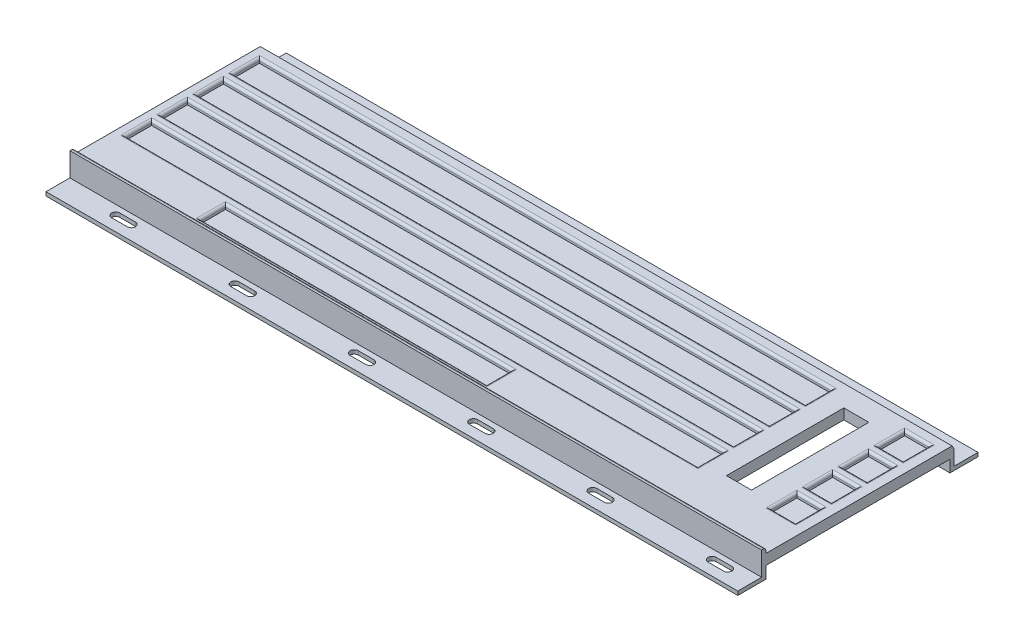
SolidWorks part; units mm, degrees
ref_plane "Front Plane" through (0, 0, 0) normal (0, 0, 1) x (1, 0, 0)
ref_plane "Top Plane" through (0, 0, 0) normal (0, 1, 0) x (1, 0, 0)
ref_plane "Right Plane" through (0, 0, 0) normal (1, 0, 0) x (0, 0, -1)
sketch "Sketch1" plane through (0, 0, 0) normal (0, 1, 0) x (1, 0, 0)
  line L1 (-184.15, 49.022) -> (184.15, 49.022)
  line L2 (-184.15, 49.022) -> (-184.15, -49.022)
  line L3 (-184.15, -49.022) -> (184.15, -49.022)
  line L4 (184.15, 49.022) -> (184.15, -49.022)
  line L5 (-184.15, 49.022) -> (184.15, -49.022) construction
  line L6 (-184.15, -49.022) -> (184.15, 49.022) construction
  point P0 (0, 0)
  dimension "D1" = 368.3
  dimension "D2" = 98.044
extrude "Boss-Extrude1" add sketch "Sketch1" along normal blind 3.175
sketch "Sketch2" plane through (0, 3.175, 0) normal (0, 1, 0) x (1, 0, 0)
  line L0 (184.15, -49.022) -> (184.15, 49.022) construction
  line L1 (-184.15, 49.022) -> (184.15, 49.022)
  line L2 (-184.15, 49.022) -> (-184.15, 44.577)
  line L3 (-184.15, 44.577) -> (184.15, 44.577)
  line L4 (184.15, 49.022) -> (184.15, 44.577)
  line L5 (-184.15, 49.022) -> (184.15, 44.577) construction
  line L6 (-184.15, 44.577) -> (184.15, 49.022) construction
  point P4 (0, 46.7995)
  dimension "D1" = 4.445
extrude "Boss-Extrude2" add sketch "Sketch2" along normal blind 2.3813
sketch "Sketch3" plane through (0, 3.175, 0) normal (0, 1, 0) x (1, 0, 0)
  line L0 (-184.15, 44.577) -> (-184.15, -49.022) construction
  line L1 (184.15, -49.022) -> (-184.15, -49.022)
  line L2 (184.15, -49.022) -> (184.15, -45.212)
  line L3 (184.15, -45.212) -> (-184.15, -45.212)
  line L4 (-184.15, -49.022) -> (-184.15, -45.212)
  line L5 (184.15, -49.022) -> (-184.15, -45.212) construction
  line L6 (184.15, -45.212) -> (-184.15, -49.022) construction
  point P5 (0, -47.117)
  dimension "D1" = 3.81
extrude "Boss-Extrude3" add sketch "Sketch3" along normal blind 2.3813
sketch "Sketch4" plane through (0, 3.175, 0) normal (0, 1, 0) x (1, 0, 0)
  line L0 (184.15, -45.212) -> (184.15, 44.577) construction
  line L1 (184.15, -31.877) -> (-184.15, -31.877)
  line L2 (184.15, -31.877) -> (184.15, -26.797)
  line L3 (184.15, -26.797) -> (-184.15, -26.797)
  line L4 (-184.15, -31.877) -> (-184.15, -26.797)
  line L5 (184.15, -31.877) -> (-184.15, -26.797) construction
  line L6 (184.15, -26.797) -> (-184.15, -31.877) construction
  line L7 (-184.15, 44.577) -> (-184.15, -45.212) construction
  point P4 (0, -29.337)
  dimension "D1" = 17.145
  dimension "D2" = 5.08
extrude "Boss-Extrude4" add sketch "Sketch4" along normal blind 2.3813
sketch "Sketch5" plane through (0, 3.175, 0) normal (0, 1, 0) x (1, 0, 0)
  line L0 (184.15, -26.797) -> (184.15, 44.577) construction
  line L1 (184.15, -12.827) -> (-184.15, -12.827)
  line L2 (184.15, -12.827) -> (184.15, -7.747)
  line L3 (184.15, -7.747) -> (-184.15, -7.747)
  line L4 (-184.15, -12.827) -> (-184.15, -7.747)
  line L5 (184.15, -12.827) -> (-184.15, -7.747) construction
  line L6 (184.15, -7.747) -> (-184.15, -12.827) construction
  line L7 (-184.15, 44.577) -> (-184.15, -26.797) construction
  point P4 (0, -10.287)
  dimension "D1" = 36.195
  dimension "D2" = 5.08
extrude "Boss-Extrude5" add sketch "Sketch5" along normal blind 2.3813
sketch "Sketch7" plane through (0, 3.175, 0) normal (0, 1, 0) x (1, 0, 0)
  line L0 (184.15, -7.747) -> (184.15, 44.577) construction
  line L1 (184.15, 6.223) -> (-184.15, 6.223)
  line L2 (184.15, 6.223) -> (184.15, 11.303)
  line L3 (184.15, 11.303) -> (-184.15, 11.303)
  line L4 (-184.15, 6.223) -> (-184.15, 11.303)
  line L5 (184.15, 6.223) -> (-184.15, 11.303) construction
  line L6 (184.15, 11.303) -> (-184.15, 6.223) construction
  line L7 (-184.15, 44.577) -> (-184.15, -7.747) construction
  point P4 (0, 8.763)
  dimension "D1" = 55.245
  dimension "D2" = 5.08
extrude "Boss-Extrude6" add sketch "Sketch7" along normal blind 2.3813
sketch "Sketch9" plane through (0, 3.175, 0) normal (0, 1, 0) x (1, 0, 0)
  line L0 (184.15, 11.303) -> (184.15, 44.577) construction
  line L1 (184.15, 25.4) -> (-184.15, 25.4)
  line L2 (184.15, 25.4) -> (184.15, 30.48)
  line L3 (184.15, 30.48) -> (-184.15, 30.48)
  line L4 (-184.15, 25.4) -> (-184.15, 30.48)
  line L5 (184.15, 25.4) -> (-184.15, 30.48) construction
  line L6 (184.15, 30.48) -> (-184.15, 25.4) construction
  point P4 (0, 27.94)
  dimension "D1" = 74.422
  dimension "D2" = 5.08
extrude "Boss-Extrude7" add sketch "Sketch9" along normal blind 2.3813
sketch "Sketch10" plane through (0, 3.175, 0) normal (0, 1, 0) x (1, 0, 0)
  line L0 (184.15, -45.212) -> (-184.15, -45.212) construction
  line L1 (184.15, 44.577) -> (177.8, 44.577)
  line L2 (184.15, 44.577) -> (184.15, -45.212)
  line L3 (184.15, -45.212) -> (177.8, -45.212)
  line L4 (177.8, 44.577) -> (177.8, -45.212)
  line L5 (184.15, 44.577) -> (177.8, -45.212) construction
  line L6 (184.15, -45.212) -> (177.8, 44.577) construction
  point P4 (180.975, -0.3175)
  dimension "D1" = 6.35
extrude "Boss-Extrude8" add sketch "Sketch10" along normal blind 2.3813
sketch "Sketch11" plane through (0, 3.175, 0) normal (0, 1, 0) x (1, 0, 0)
  line L0 (-184.15, 44.577) -> (177.8, 44.577) construction
  line L1 (-184.15, -45.212) -> (-179.07, -45.212)
  line L2 (-184.15, -45.212) -> (-184.15, 44.577)
  line L3 (-184.15, 44.577) -> (-179.07, 44.577)
  line L4 (-179.07, -45.212) -> (-179.07, 44.577)
  line L5 (-184.15, -45.212) -> (-179.07, 44.577) construction
  line L6 (-184.15, 44.577) -> (-179.07, -45.212) construction
  point P5 (-181.61, -0.3175)
  dimension "D1" = 5.08
extrude "Boss-Extrude9" add sketch "Sketch11" along normal blind 2.3813
sketch "Sketch12" plane through (0, 3.175, 0) normal (0, 1, 0) x (1, 0, 0)
  line L0 (-179.07, 44.577) -> (177.8, 44.577) construction
  line L1 (164.465, 44.577) -> (150.495, 44.577)
  line L2 (164.465, 44.577) -> (164.465, -45.212)
  line L3 (164.465, -45.212) -> (150.495, -45.212)
  line L4 (150.495, 44.577) -> (150.495, -45.212)
  line L5 (164.465, 44.577) -> (150.495, -45.212) construction
  line L6 (164.465, -45.212) -> (150.495, 44.577) construction
  line L7 (177.8, -45.212) -> (-179.07, -45.212) construction
  point P4 (157.48, -0.3175)
  dimension "D1" = 19.685
  dimension "D2" = 13.97
extrude "Boss-Extrude10" add sketch "Sketch12" along normal blind 2.3813
sketch "Sketch13" plane through (0, 3.175, 0) normal (0, 1, 0) x (1, 0, 0)
  line L0 (-179.07, 44.577) -> (150.495, 44.577) construction
  line L1 (138.43, 44.577) -> (125.73, 44.577)
  line L2 (138.43, 44.577) -> (138.43, -45.212)
  line L3 (138.43, -45.212) -> (125.73, -45.212)
  line L4 (125.73, 44.577) -> (125.73, -45.212)
  line L5 (138.43, 44.577) -> (125.73, -45.212) construction
  line L6 (138.43, -45.212) -> (125.73, 44.577) construction
  line L7 (150.495, -45.212) -> (-179.07, -45.212) construction
  line L8 (184.15, -49.022) -> (184.15, 49.022) construction
  point P4 (132.08, -0.3175)
  dimension "D1" = 45.72
  dimension "D2" = 12.7
extrude "Boss-Extrude11" add sketch "Sketch13" along normal blind 2.3813
sketch "Sketch14" plane through (0, 5.5563, 0) normal (0, 1, 0) x (1, 0, 0)
  line L1 (151.13, 38.862) -> (137.795, 38.862)
  line L2 (151.13, 38.862) -> (151.13, -23.622)
  line L3 (151.13, -23.622) -> (137.795, -23.622)
  line L4 (137.795, 38.862) -> (137.795, -23.622)
  line L5 (151.13, 38.862) -> (137.795, -23.622) construction
  line L6 (151.13, -23.622) -> (137.795, 38.862) construction
  line L7 (184.15, 49.022) -> (-184.15, 49.022) construction
  point P4 (144.4625, 7.62)
  dimension "D1" = 10.16
  dimension "D2" = 25.4
  dimension "D3" = 33.02
  dimension "D4" = 13.335
extrude "Cut-Extrude1" cut sketch "Sketch14" against normal through all
sketch "Sketch15" plane through (0, 3.175, 0) normal (0, 1, 0) x (1, 0, 0)
  line L1 (138.43, -45.212) -> (150.495, -45.212)
  line L2 (138.43, -45.212) -> (138.43, -31.877)
  line L3 (138.43, -31.877) -> (150.495, -31.877)
  line L4 (150.495, -45.212) -> (150.495, -31.877)
  line L5 (138.43, -45.212) -> (150.495, -31.877) construction
  line L6 (138.43, -31.877) -> (150.495, -45.212) construction
  point P5 (144.4625, -38.5445)
extrude "Boss-Extrude12" add sketch "Sketch15" along normal blind 2.3813
sketch "Sketch16" plane through (0, 3.175, 0) normal (0, 1, 0) x (1, 0, 0)
  line L1 (138.43, -26.797) -> (150.495, -26.797)
  line L2 (138.43, -26.797) -> (138.43, -23.622)
  line L3 (138.43, -23.622) -> (150.495, -23.622)
  line L4 (150.495, -26.797) -> (150.495, -23.622)
  line L5 (138.43, -26.797) -> (150.495, -23.622) construction
  line L6 (138.43, -23.622) -> (150.495, -26.797) construction
  point P4 (144.4625, -25.2095)
extrude "Boss-Extrude13" add sketch "Sketch16" along normal blind 2.3813
sketch "Sketch17" plane through (0, 3.175, 0) normal (0, 1, 0) x (1, 0, 0)
  line L1 (138.43, 44.577) -> (150.495, 44.577)
  line L2 (138.43, 44.577) -> (138.43, 38.862)
  line L3 (138.43, 38.862) -> (150.495, 38.862)
  line L4 (150.495, 44.577) -> (150.495, 38.862)
  line L5 (138.43, 44.577) -> (150.495, 38.862) construction
  line L6 (138.43, 38.862) -> (150.495, 44.577) construction
  point P4 (144.4625, 41.7195)
extrude "Boss-Extrude14" add sketch "Sketch17" along normal blind 2.3813
sketch "Sketch18" plane through (0, 3.175, 0) normal (0, 1, 0) x (1, 0, 0)
  line L1 (164.465, -31.877) -> (177.8, -31.877)
  line L2 (164.465, -31.877) -> (164.465, -45.212)
  line L3 (164.465, -45.212) -> (177.8, -45.212)
  line L4 (177.8, -31.877) -> (177.8, -45.212)
  line L5 (164.465, -31.877) -> (177.8, -45.212) construction
  line L6 (164.465, -45.212) -> (177.8, -31.877) construction
  point P5 (171.1325, -38.5445)
extrude "Boss-Extrude15" add sketch "Sketch18" along normal blind 2.3813
sketch "Sketch19" plane through (0, 3.175, 0) normal (0, 1, 0) x (1, 0, 0)
  line L0 (125.73, -45.212) -> (-179.07, -45.212) construction
  line L1 (-179.07, -31.877) -> (-120.65, -31.877)
  line L2 (-179.07, -31.877) -> (-179.07, -45.212)
  line L3 (-179.07, -45.212) -> (-120.65, -45.212)
  line L4 (-120.65, -31.877) -> (-120.65, -45.212)
  line L5 (-179.07, -31.877) -> (-120.65, -45.212) construction
  line L6 (-179.07, -45.212) -> (-120.65, -31.877) construction
  point P4 (-149.86, -38.5445)
  dimension "D1" = 63.5
extrude "Boss-Extrude16" add sketch "Sketch19" along normal blind 2.3813
sketch "Sketch20" plane through (0, 3.175, 0) normal (0, 1, 0) x (1, 0, 0)
  line L0 (125.73, -45.212) -> (-120.65, -45.212) construction
  line L1 (125.73, -31.877) -> (31.75, -31.877)
  line L2 (125.73, -31.877) -> (125.73, -45.212)
  line L3 (125.73, -45.212) -> (31.75, -45.212)
  line L4 (31.75, -31.877) -> (31.75, -45.212)
  line L5 (125.73, -31.877) -> (31.75, -45.212) construction
  line L6 (125.73, -45.212) -> (31.75, -31.877) construction
  point P4 (78.74, -38.5445)
  dimension "D1" = 152.4
extrude "Boss-Extrude17" add sketch "Sketch20" along normal blind 2.3813
sketch "Sketch22" plane through (0, 0, 49.022) normal (0, 0, 1) x (1, 0, 0)
  line L1 (-184.15, 8.255) -> (184.15, 8.255)
  line L2 (-184.15, 8.255) -> (-184.15, -6.35)
  line L3 (-184.15, -6.35) -> (184.15, -6.35)
  line L4 (184.15, 8.255) -> (184.15, -6.35)
  line L5 (-184.15, 8.255) -> (184.15, -6.35) construction
  line L6 (-184.15, -6.35) -> (184.15, 8.255) construction
  point P4 (0, 0.9525)
  dimension "D1" = 8.255
  dimension "D2" = 6.35
  dimension "D3" = 0
  dimension "D4" = 0
extrude "Boss-Extrude18" add sketch "Sketch22" along normal blind 2.2225
sketch "Sketch23" plane through (0, 0, 51.2445) normal (0, 0, 1) x (1, 0, 0)
  line L0 (184.15, -6.35) -> (184.15, 8.255) construction
  line L1 (-184.15, -6.35) -> (184.15, -6.35)
  line L2 (-184.15, -6.35) -> (-184.15, -4.318)
  line L3 (-184.15, -4.318) -> (184.15, -4.318)
  line L4 (184.15, -6.35) -> (184.15, -4.318)
  line L5 (-184.15, -6.35) -> (184.15, -4.318) construction
  line L6 (-184.15, -4.318) -> (184.15, -6.35) construction
  point P4 (0, -5.334)
  dimension "D1" = 2.032
extrude "Boss-Extrude19" add sketch "Sketch23" along normal blind 12.7
sketch "Sketch24" plane through (0, 0, -49.022) normal (0, 0, -1) x (-1, 0, 0)
  line L1 (-184.15, 5.5563) -> (184.15, 5.5563)
  line L2 (-184.15, 5.5563) -> (-184.15, -6.35)
  line L3 (-184.15, -6.35) -> (184.15, -6.35)
  line L4 (184.15, 5.5563) -> (184.15, -6.35)
  line L5 (-184.15, 5.5563) -> (184.15, -6.35) construction
  line L6 (-184.15, -6.35) -> (184.15, 5.5563) construction
  point P4 (0, -0.3969)
  dimension "D1" = 6.35
  dimension "D2" = 0
extrude "Boss-Extrude20" add sketch "Sketch24" along normal blind 2.2225
sketch "Sketch25" plane through (0, 0, -51.2445) normal (0, 0, -1) x (-1, 0, 0)
  line L0 (184.15, -6.35) -> (184.15, 5.5563) construction
  line L1 (-184.15, -6.35) -> (184.15, -6.35)
  line L2 (-184.15, -6.35) -> (-184.15, -4.318)
  line L3 (-184.15, -4.318) -> (184.15, -4.318)
  line L4 (184.15, -6.35) -> (184.15, -4.318)
  line L5 (-184.15, -6.35) -> (184.15, -4.318) construction
  line L6 (-184.15, -4.318) -> (184.15, -6.35) construction
  point P4 (0, -5.334)
  dimension "D1" = 2.032
extrude "Boss-Extrude21" add sketch "Sketch25" along normal blind 12.7
hole_wizard "11/64 (0.17188) Diameter Slot1" positions "Sketch26" profile "Sketch27" size "11/64" standard "ANSI Inch" slot yes end condition through all
sketch "Sketch26" plane through (0, -4.318, 0) normal (0, 1, 0) x (1, 0, 0)
  line L0 (160.655, 57.5945) -> (173.355, 57.5945) construction
  line L1 (-184.15, 63.9445) -> (-184.15, 51.2445) construction
  line L2 (-184.15, -63.9445) -> (-184.15, -51.2445) construction
  line L3 (184.15, -63.9445) -> (-184.15, -63.9445) construction
  point P0 (167.005, 57.5945)
  point P4 (103.505, 57.5945)
  point P6 (59.055, 57.5945)
  point P8 (-42.545, 57.5945)
  point P10 (-86.995, 57.5945)
  point P12 (-150.495, 57.5945)
  point P14 (167.005, -56.3245)
  point P16 (103.505, -56.3245)
  point P18 (40.005, -56.3245)
  point P20 (-23.495, -56.3245)
  point P22 (-86.995, -56.3245)
  point P24 (-150.495, -56.3245)
  dimension "D1" = 12.7
  dimension "D2" = 6.35
  dimension "D3" = 7.62
  dimension "D4" = 33.655
  dimension "D5" = 33.655
  dimension "D6" = 63.5
  dimension "D7" = 44.45
  dimension "D8" = 101.6
  dimension "D9" = 44.45
  dimension "D10" = 63.5
  dimension "D11" = 63.5
  dimension "D12" = 63.5
  dimension "D13" = 63.5
  dimension "D14" = 63.5
  dimension "D15" = 63.5
  dimension "D16" = 6.35
  dimension "D17" = 6.35
  dimension "D18" = 6.35
  dimension "D19" = 6.35
  dimension "D20" = 6.35
  dimension "D21" = 7.62
  dimension "D22" = 7.62
  dimension "D23" = 7.62
  dimension "D24" = 7.62
  dimension "D25" = 7.62
sketch "Sketch27" plane through (167.005, -4.318, -57.5945) normal (1, 0, 0) x (0, 0, 1)
  line L0 (0, 0) -> (0, 2.032)
  line L1 (0, 2.032) -> (2.1829, 2.032)
  line L2 (2.1829, 2.032) -> (2.1829, 0)
  line L5 (2.1829, 0) -> (0, 0)
  line L11 (0, -6.35) -> (0, 107.95) construction
  dimension "Thru Hole Dia." = 4.3658
  dimension "Thru Hole Depth" = 2.032
fillet "Fillet2" radius 1.27 37 edges at (-120.65, 5.5563, 38.5445) (-179.07, 5.5563, 19.812) (-179.07, 5.5563, 0.762) (-179.07, 5.5563, -18.3515) (-179.07, 5.5563, -37.5285) (31.75, 5.5563, 38.5445) (125.73, 5.5563, 19.812) (125.73, 5.5563, 0.762) (125.73, 5.5563, -18.3515) (125.73, 5.5563, -37.5285) (164.465, 5.5563, -37.5285) (177.8, 5.5563, -37.5285) (164.465, 5.5563, -18.3515) (177.8, 5.5563, -18.3515) (177.8, 5.5563, 0.762) (164.465, 5.5563, 0.762) (164.465, 5.5563, 19.812) (177.8, 5.5563, 19.812) (171.1325, 5.5563, 26.797) (171.1325, 5.5563, 12.827) (171.1325, 5.5563, 7.747) (171.1325, 5.5563, -6.223) (171.1325, 5.5563, -11.303) (171.1325, 5.5563, -25.4) (171.1325, 5.5563, -30.48) (171.1325, 5.5563, -44.577) (-44.45, 5.5563, 45.212) (-44.45, 5.5563, 31.877) (0, 8.255, 49.022) (-26.67, 5.5563, 26.797) (-26.67, 5.5563, 12.827) (-26.67, 5.5563, 7.747) (-26.67, 5.5563, -6.223) (-26.67, 5.5563, -11.303) (-26.67, 5.5563, -25.4) (-26.67, 5.5563, -30.48) (-26.67, 5.5563, -44.577)
chamfer "Chamfer1" distance 1.905 angle 30 1 edges at (0, 5.5563, -51.2445) first distance on face at (0, 0.6191, -51.2445)
